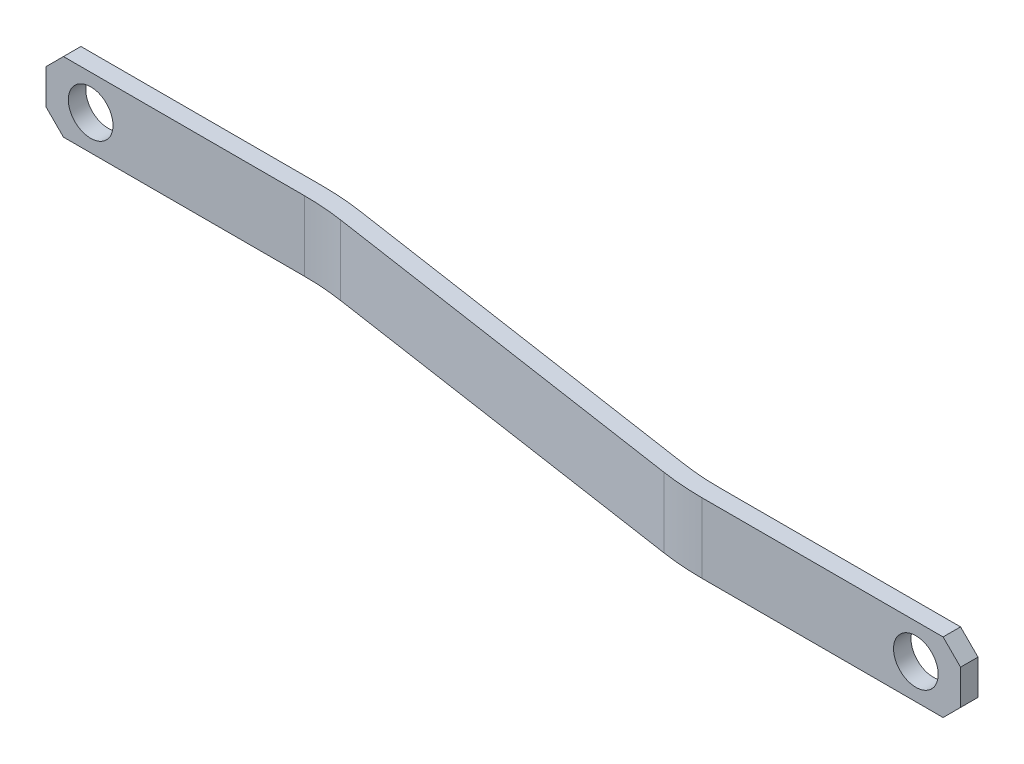
SolidWorks part; units mm, degrees
ref_plane "Plane1" through (0, 0, 0) normal (0, 0, 1) x (1, 0, 0)
ref_plane "Plane2" through (0, 0, 0) normal (0, 1, 0) x (1, 0, 0)
ref_plane "Plane3" through (0, 0, 0) normal (1, 0, 0) x (0, 0, -1)
other "Configuration Table"
sketch "Sketch1" plane through (0, 0, 0) normal (0, 0, 1) x (1, 0, 0)
  line L0 (0, 0) -> (177.8, 0)
  line L1 (0, 0) -> (0, 12.7)
  line L2 (177.8, 12.7) -> (0, 12.7)
  line L3 (177.8, 12.7) -> (177.8, 0)
  dimension "D1" = 12.7
  dimension "D2" = 177.8
extrude "Base-Extrude" add sketch "Sketch1" along normal blind 14.605
sketch "Sketch5" plane through (0, 12.7, 0) normal (0, 1, 0) x (-1, 0, 0)
  line L0 (0, 0) -> (-47.0228, 0)
  line L1 (-54.5357, 0.5586) -> (-123.7339, 10.9063)
  line L2 (-130.7772, 11.43) -> (-177.8, 11.43)
  line L3 (-177.8, 0) -> (0, 0) construction
  line L5 (-177.8, 14.605) -> (-177.8, 0) construction
  line L6 (-177.8, 14.605) -> (0, 14.605) construction
  line L7 (0, 3.175) -> (-47.0228, 3.175)
  line L8 (-54.0661, 3.6987) -> (-123.2643, 14.0464)
  line L9 (-130.7772, 14.605) -> (-177.8, 14.605)
  line L10 (0, 3.175) -> (0, 0)
  line L11 (-177.8, 14.605) -> (-177.8, 11.43)
  line L12 (-50.5639, 3.175) -> (-127, 14.605) construction
  line L13 (-127, 14.605) -> (-177.8, 14.605) construction
  line L14 (0, 0) -> (-50.8, 0) construction
  line L15 (-50.8, 0) -> (-127.2361, 11.43) construction
  line L16 (-127.2361, 11.43) -> (-177.8, 11.43) construction
  line L17 (0, 3.175) -> (-50.5639, 3.175) construction
  arc A0 (-123.2643, 14.0464) -> (-130.7772, 14.605) centre (-130.7772, -36.195) ccw
  arc A1 (-47.0228, 0) -> (-54.5357, 0.5586) centre (-47.0228, 50.8) cw
  arc A2 (-123.7339, 10.9063) -> (-130.7772, 11.43) centre (-130.7772, -36.195) ccw
  arc A3 (-47.0228, 3.175) -> (-54.0661, 3.6987) centre (-47.0228, 50.8) cw
  point P28 (-127, 14.605)
  point P29 (-50.8, 0)
  dimension "D5" = 50.8
  dimension "D1" = 47.625
  dimension "D2" = 50.8
  dimension "D3" = 3.175
  dimension "D6" = 50.8
  dimension "D4" = 3.175
extrude "Extrude1" add sketch "Sketch5" against normal blind 50.8 separate body
combine bodies "Combine1" operation type common bodies to combine 101 104
sketch "Sketch2" plane through (0, 0, 3.175) normal (0, 0, 1) x (1, 0, 0)
  line L0 (0, 6.35) -> (17.2602, 6.35) construction
  line L2 (0, 0) -> (0, 12.7) construction
  circle A0 centre (8.128, 6.35) radius 4.064
  dimension "D1" = 8.128
  dimension "D2" = 8.128
extrude "Cut-Extrude1" cut sketch "Sketch2" against normal through all
sketch "Sketch3" plane through (185.2696, -0.2287, 11.43) normal (0, 0, 1) x (1, 0, 0)
  line L0 (-25.4, 6.5787) -> (-7.4696, 6.5787) construction
  line L3 (-7.4696, 12.9287) -> (-7.4696, 0.2287) construction
  circle A0 centre (-15.5976, 6.5787) radius 4.064
  dimension "D1" = 8.128
  dimension "D2" = 8.128
extrude "Cut-Extrude2" cut sketch "Sketch3" along normal through all
chamfer "Chamfer1" distance 3.175 angle 45 2 edges at (177.8, 12.7, 13.0175) (177.8, 0, 13.0175)
chamfer "Chamfer2" distance 3.175 angle 45 2 edges at (0, 12.7, 1.5875) (0, 0, 1.5875)
